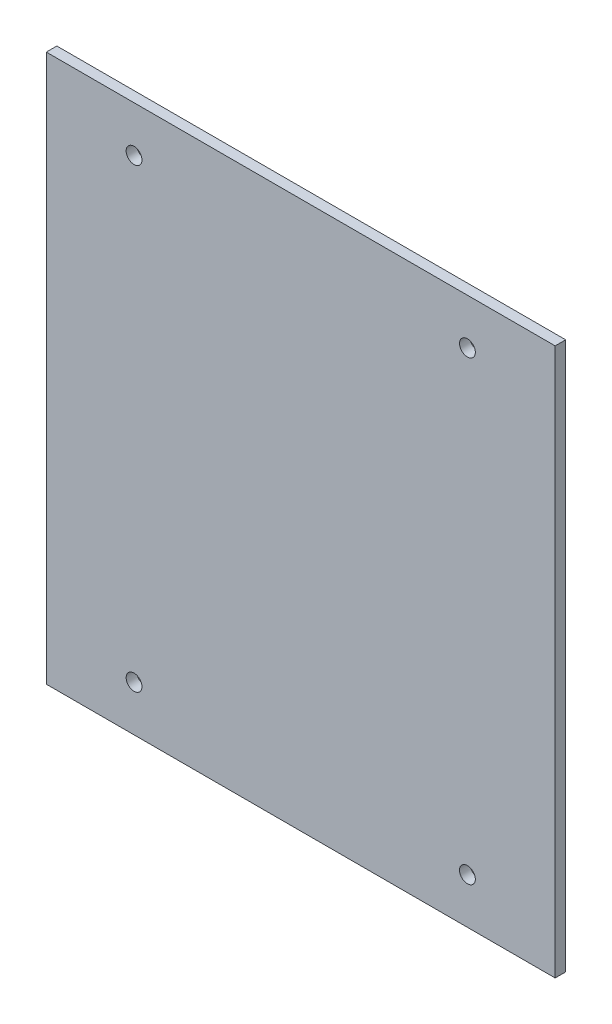
SolidWorks part; units mm, degrees
ref_plane "Ebene vorne" through (0, 0, 0) normal (0, 0, 1) x (1, 0, 0)
ref_plane "Ebene oben" through (0, 0, 0) normal (0, 1, 0) x (1, 0, 0)
ref_plane "Ebene rechts" through (0, 0, 0) normal (1, 0, 0) x (0, 0, -1)
sketch "Skizze1" plane through (0, 0, 0) normal (0, 0, 1) x (1, 0, 0)
  line L1 (72.5, -78) -> (-72.5, -78)
  line L2 (72.5, -78) -> (72.5, 78)
  line L3 (72.5, 78) -> (-72.5, 78)
  line L4 (-72.5, -78) -> (-72.5, 78)
  line L5 (72.5, -78) -> (-72.5, 78) construction
  line L6 (72.5, 78) -> (-72.5, -78) construction
  point P0 (0, 0)
  dimension "D1" = 156
  dimension "D2" = 145
extrude "Aufsatz-Linear austragen1" add sketch "Skizze1" along normal blind 3
hole_wizard "Durchgangsloch für M41" positions "Skizze2" profile "Skizze3" hole size "M4" standard "DIN"
sketch "Skizze2" plane through (0, 0, 3) normal (0, 0, 1) x (1, 0, 0)
  line L0 (-72.5, 78) -> (-72.5, -78) construction
  line L3 (-72.5, -78) -> (72.5, -78) construction
  line L4 (72.5, -78) -> (72.5, 78) construction
  line L5 (1.65, 0) -> (-1.65, 0) construction
  point P6 (-47.5, -65)
  point P25 (47.5, -65)
  point P38 (47.5, 65)
  point P39 (-47.5, 65)
  dimension "D3" = 25
  dimension "D4" = 13
  dimension "D5" = 25
  dimension "D6" = 13
sketch "Skizze3" plane through (-47.5, -65, 3) normal (1, 0, 0) x (0, -1, 0)
  line L0 (0, 0) -> (0, 4.3519)
  line L1 (0, 4.3519) -> (2.25, 3)
  line L2 (2.25, 3) -> (2.25, 0)
  line L5 (2.25, 0) -> (0, 0)
  line L10 (0, 4.3519) -> (-2.25, 3) construction
  line L11 (0, -6.35) -> (0, 107.95) construction
  dimension "Bohrerdurchmesser" = 4.5
  dimension "Bohrungstiefe" = 3
  dimension "Spitzenwinkel" = 118
